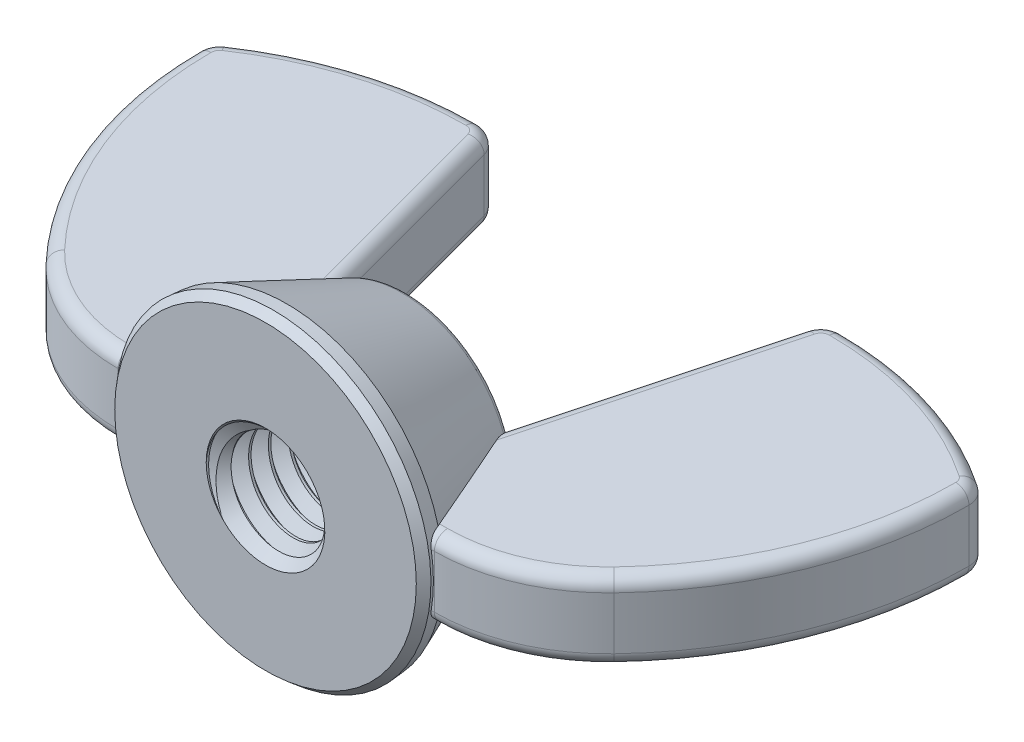
SolidWorks part; units mm, degrees
ref_plane "Front Plane" through (0, 0, 0) normal (0, 0, 1) x (1, 0, 0)
ref_plane "Top Plane" through (0, 0, 0) normal (0, 1, 0) x (1, 0, 0)
ref_plane "Right Plane" through (0, 0, 0) normal (1, 0, 0) x (0, 0, -1)
sketch "Sketch1" plane through (0, 0, 0) normal (0, 0, 1) x (1, 0, 0)
  circle A0 centre (0, 0) radius 1.5
  circle A1 centre (0, 0) radius 4
  dimension "D1" = 8
sketch "Sketch2" plane through (0, 0, 0) normal (0, 1, 0) x (1, 0, 0)
  line L0 (0, 0) -> (0, 10) construction
  line L1 (-1.5, 0) -> (1.5, 0) construction
  line L2 (-9.75, 10) -> (9.75, 10) construction
  line L3 (9.75, 10) -> (9.75, 0) construction
  line L4 (-9.75, 10) -> (-9.75, 0) construction
  line L5 (-9.75, 0) -> (9.75, 0) construction
  line L6 (-2.7274, 3.6) -> (2.7274, 3.6) construction
  line L7 (0, 0) -> (0, 3.6) construction
  line L8 (-4.3144, 0.54) -> (4, 0.54) construction
  line L9 (4, 0) -> (4, 3.6) construction
  line L10 (2.4547, 3.6) -> (4.2081, 10.1439)
  line L12 (2.7274, 3.6) -> (2.7274, 0.27) construction
  line L13 (-4, 0) -> (4, 0) construction
  line L14 (4, 0.54) -> (2.7274, 3.6) construction
  line L15 (4.2081, 10.1439) -> (10.0115, 8.3697)
  line L16 (10.0115, 8.3697) -> (5.5453, 0.27)
  line L17 (4, 0.27) -> (5.5453, 0.27)
  line L19 (2.4547, 0.27) -> (4, 0.27)
  line L20 (-2.4547, 3.6) -> (2.4547, 3.6) construction
  line L21 (2.4547, 3.6) -> (2.4547, 0.27)
  circle A3 centre (9.1944, 8.0385) radius 0.5556 construction
  circle A4 centre (4.5958, 9.4444) radius 0.5556 construction
  dimension "D6" = 1.1111
  dimension "D2" = 3.6
  dimension "D4" = 5.4548
  dimension "D1" = 0.54
  dimension "D3" = 22.582
  dimension "D5" = 0.27
  dimension "D8" = 17
  dimension "D9" = 4.9093
  dimension "D7" = 15
sketch "Sketch13" plane through (0, 0, 0) normal (0, 1, 0) x (1, 0, 0)
  line L1 (2.4547, 3.6) -> (2.4547, 0.27) construction
  line L2 (2.4547, 3.6) -> (4.2081, 10.1439) construction
  line L3 (-9.75, 10) -> (9.75, 10) construction
  line L4 (9.75, 10) -> (9.75, 0) construction
  line L5 (4, 0.27) -> (5.5453, 0.27) construction
  line L6 (2.4547, 0.27) -> (4, 0.27) construction
  line L7 (0, 0) -> (0, 3.6) construction
  line L8 (-1.5, 0) -> (1.5, 0) construction
  line L9 (0, 0) -> (0, 10) construction
  line L10 (-2.7274, 3.6) -> (2.7274, 3.6) construction
  line L11 (2.4547, 0.27) -> (4, 0.27)
  line L12 (2.4547, 3.6) -> (2.4547, 0.27)
  line L13 (2.4547, 3.6) -> (4.0592, 9.5882)
  circle A0 centre (9.1944, 8.0385) radius 0.5556 construction
  circle A1 centre (4.5958, 9.4444) radius 0.5556 construction
  arc A5 (9.75, 8.0385) -> (9.5051, 8.4991) centre (9.1944, 8.0385) ccw
  arc A6 (4.5958, 10) -> (4.0592, 9.5882) centre (4.5958, 9.4444) ccw
  arc A7 (7.1841, 1.6328) -> (9.75, 8.0385) centre (0.4711, 8.0385) ccw
  arc A8 (9.5051, 8.4991) -> (4.5958, 10) centre (4.5958, 1.2208) ccw
  arc A10 (4, 0.27) -> (7.1841, 1.6328) centre (4, 4.6712) ccw
extrude "Extrude2" add sketch "Sketch13" along normal mid plane 2
sketch "Sketch3" plane through (0, 0, 0) normal (0, 0, 1) x (1, 0, 0)
  circle A0 centre (0, 0) radius 4 construction
  circle A1 centre (0, 0) radius 4
extrude "Extrude1" add sketch "Sketch3" against normal up to vertex (0.54 mm away) draft 5 separate body up to point (4, 0, -0.54)
sketch "Sketch15" plane through (0, 0, -0.54) normal (0, 0, -1) x (-1, 0, 0)
  circle A1 centre (0, 0) radius 3.9528
  circle A2 centre (0, 0) radius 3.9528
  dimension "D1" = 0
extrude "Extrude3" add sketch "Sketch15" along normal up to vertex (3.06 mm away) draft 22.582 up to point (0, 0, -3.6)
fillet "Fillet3" radius 0.254 1 edges at (-2.6802, 0, -3.6)
sketch "Sketch12" plane through (0, 0, -3.6) normal (0, 0, -1) x (-1, 0, 0)
  circle A1 centre (0, 0) radius 3.9528
  circle A2 centre (0, 0) radius 3.9528 construction
  dimension "D1" = 7.9055
sketch "Sketch4" plane through (0, 0, 0) normal (0, 0, 1) x (1, 0, 0)
  circle A0 centre (0, 0) radius 1.5 construction
  circle A1 centre (0, 0) radius 1.5
extrude "Cut-Extrude1" cut sketch "Sketch4" against normal through all
sketch "Sketch5" plane through (0, 0, 0) normal (0, 0, 1) x (1, 0, 0)
  circle A0 centre (0, 0) radius 1.5 construction
  circle A1 centre (0, 0) radius 1.5
curve "Helix/Spiral1" pitch 0.5 height 5.6 radius 1.5 centre (0, 0, 0) axis (0, 0, -1) start towards (1, 0, 0) parameters "pitch"=0.5
sketch "Sketch6" plane through (0, 0, 0) normal (0, 1, 0) x (1, 0, 0)
  line L0 (-1.5, -0.4375) -> (-1.1752, -0.25)
  line L1 (-1.1752, -0.25) -> (-1.1752, -0.1875)
  line L2 (-1.1752, -0.1875) -> (-1.5, 0)
  line L3 (-1.5, -0.4375) -> (-1.5, 0)
  line L4 (-1.5, -0.2188) -> (-1.1752, -0.2188) construction
  line L5 (-1.3376, -0.3438) -> (-1.3376, -0.0938) construction
  line L6 (-1.5, 0) -> (1.5, 0) construction
  dimension "D1" = 60
  dimension "D2" = 0.0625
  dimension "D3" = 0.25
sweep "Sweep1" add profiles "Sketch6" path "Helix/Spiral1"
sketch "Sketch7" plane through (0, 0, 0) normal (0, 0, 1) x (1, 0, 0)
  circle A1 centre (0, 0) radius 4
  circle A2 centre (0, 0) radius 4
  dimension "D1" = 0
extrude "Cut-Extrude2" cut sketch "Sketch7" along normal through all
ref_plane "Plane1" through (0, 0, -3.6) normal (0, 0, 1) x (1, 0, 0)
sketch "Sketch8" plane through (0, 0, -3.6) normal (0, 0, 1) x (1, 0, 0)
  circle A0 centre (0, 0) radius 3.9528 construction
  circle A2 centre (0, 0) radius 3.9528
extrude "Cut-Extrude3" cut sketch "Sketch8" against normal through all
sketch "Sketch9" plane through (0, 0, 0) normal (0, 0, 1) x (1, 0, 0)
  circle A1 centre (0, 0) radius 1.5
  circle A2 centre (0, 0) radius 1.5
  dimension "D1" = 0
extrude "Cut-Extrude4" cut sketch "Sketch9" against normal through all draft 45
sketch "Sketch11" plane through (0, 0, -3.6) normal (0, 0, 1) x (1, 0, 0)
  circle A0 centre (0, 0) radius 1.5 construction
  circle A1 centre (0, 0) radius 1.4492
  circle A2 centre (0, 0) radius 1.5 construction
  dimension "D1" = 0.0508
extrude "Cut-Extrude5" cut sketch "Sketch11" along normal through all draft 45
chamfer "Chamfer1" distance 0.2025 angle 45 1 edges at (4, 0, 0) first distance on face at (-3.9528, 0, -0.54)
fillet "Fillet4" radius 0.3333 14 edges at (3.2273, 1, -0.27) (5.7318, 1, -0.625) (4.2576, 1, -9.8852) (7.1626, 1, -9.6164) (9.685, 1, -8.2993) (3.2273, -1, -0.27) (5.7318, -1, -0.625) (4.2576, -1, -9.8852) (7.1626, -1, -9.6164) (9.685, -1, -8.2993) (9.0847, 1, -4.5883) (9.0847, -1, -4.5883) (3.2569, 1, -6.5941) (3.2569, -1, -6.5941)
mirror "Mirror6" about plane through (0, 0, 0) normal (1, 0, 0) of bodies 108 113
combine bodies "Combine2" operation type add bodies to combine 116 108 107
equation "\"D1@Sketch1\" = \"thread dia@Sketch1\"*1.725"
equation "\"D2@Sketch2\" = \"B@Sketch2\"*.36"
equation "\"D3@Helix/Spiral1\" = \"D2@Sketch2\"+2"
equation "\"D2@Sketch6\" = \"pitch@Helix/Spiral1\"*.125"
equation "\"D3@Sketch6\" = \"pitch@Helix/Spiral1\"*.5"
equation "\"D4@Sketch2\" = \"D1@Sketch12\"*.69"
equation "\"D1@Extrude2\" = \"D1@Sketch1\"*.25"
equation "\"D1@Sketch2\" = \"D2@Sketch2\"*.150"
equation "\"D5@Sketch2\" = \"D1@Sketch2\"/2"
equation "\"D3@Extrude3\" = \"D3@Sketch2\""
equation "\"D1@Chamfer1\" = \"D5@Sketch2\"*.75"
equation "\"D9@Sketch2\" = \"D4@Sketch2\"*.9"
equation "\"D6@Sketch2\" = \"D1@Extrude2\"/1.8"
equation "\"D1@Fillet4\" = \"D1@Extrude2\"/6"
